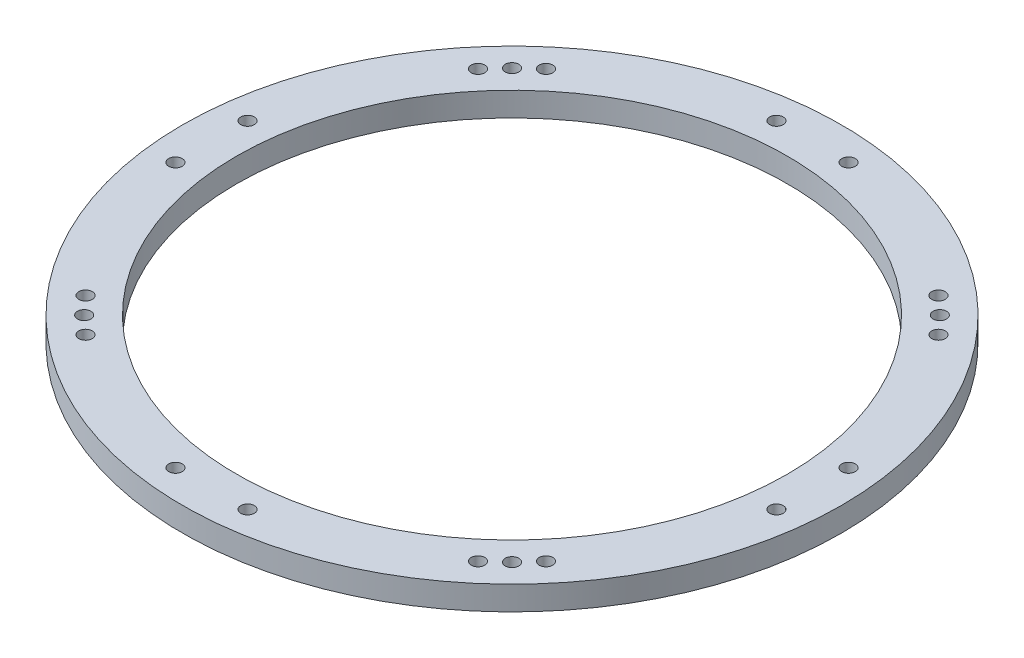
SolidWorks part; units mm, degrees
material "Oak"
ref_plane "Front Plane" through (0, 0, 0) normal (0, 0, 1) x (1, 0, 0)
ref_plane "Top Plane" through (0, 0, 0) normal (0, 1, 0) x (1, 0, 0)
ref_plane "Right Plane" through (0, 0, 0) normal (1, 0, 0) x (0, 0, -1)
sketch "Sketch1" plane through (0, 0, 0) normal (0, 0, 1) x (1, 0, 0)
  line L0 (0, -200000) -> (0, 218797.9879) construction
  line L5 (0, -200000) -> (0, 218797.9879) construction
  line L6 (174.1012, 207.3685) -> (174.1012, 194.6685)
  line L7 (145.5262, 207.3685) -> (174.1012, 207.3685)
  line L8 (174.1012, 194.6685) -> (145.5262, 194.6685)
  line L9 (145.5262, 194.6685) -> (145.5262, 207.3685)
revolve "Revolve1" add sketch "Sketch1" angle 360 about L5
hole_wizard "9/32 (0.28125) Diameter Hole1" positions "Sketch5" profile "Sketch6" hole size "9/32" standard "ANSI Inch" end condition through all
sketch "Sketch5" plane through (0, 207.3685, 0) normal (0, 1, 0) x (1, 0, 0)
  point P0 (-113.0054, 113.0054)
  point P3 (-103.6677, 121.6282)
  point P6 (-121.6282, 103.6677)
sketch "Sketch6" plane through (-113.0054, 207.3685, -113.0054) normal (1, 0, 0) x (0, 0, 1)
  line L0 (0, 0) -> (0, 12.7)
  line L1 (0, 12.7) -> (3.5719, 12.7)
  line L2 (3.5719, 12.7) -> (3.5719, 0)
  line L5 (3.5719, 0) -> (0, 0)
  line L11 (0, -6.35) -> (0, 107.95) construction
  dimension "Thru Hole Dia." = 7.1437
  dimension "Thru Hole Depth" = 12.7
sketch "Sketch7" plane through (0, 207.3685, 0) normal (0, 1, 0) x (1, 0, 0)
  line L0 (0, 0) -> (158.75, 0) construction
  line L1 (158.75, 19.05) -> (158.75, -19.05) construction
  circle A0 centre (158.75, -19.05) radius 3.5719
  circle A1 centre (158.75, 19.05) radius 3.5719
  point P6 (158.75, 0)
  dimension "D3" = 7.1437
  dimension "D1" = 38.1
  dimension "D2" = 158.75
extrude "Cut-Extrude1" cut sketch "Sketch7" against normal through all
pattern_circular "CirPattern1" count 4 over 360 about axis through (0, -200000, 0) along (0, -1, 0) of "9/32 (0.28125) Diameter Hole1", "Cut-Extrude1"
